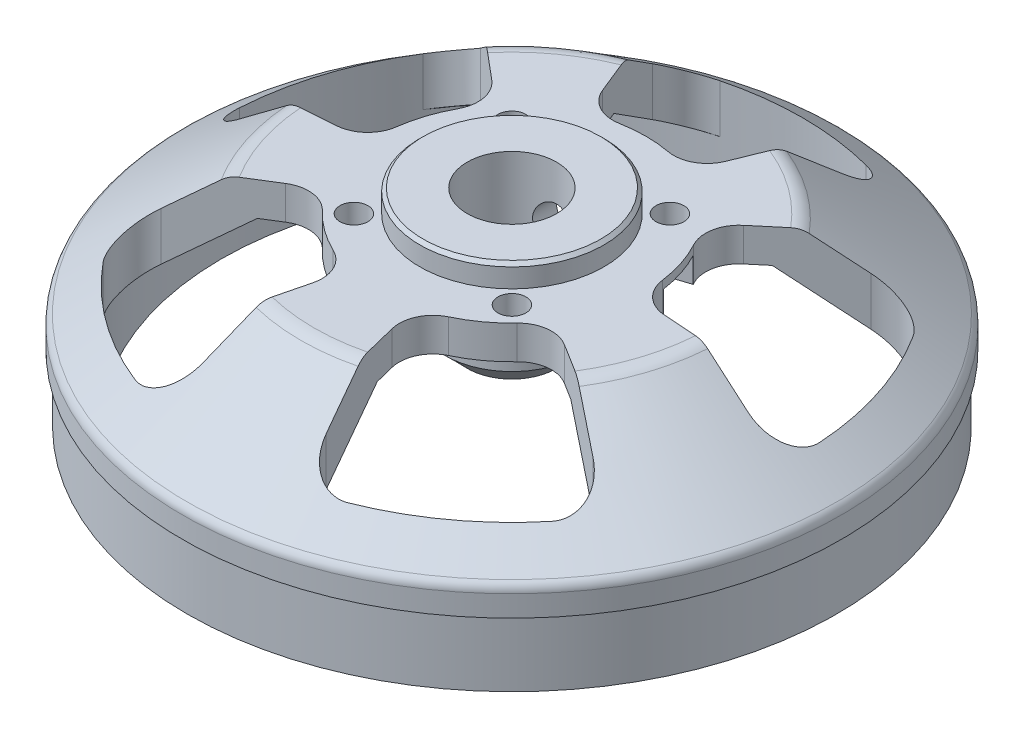
SolidWorks part; units mm, degrees
ref_plane "Front Plane" through (0, 0, 0) normal (0, 0, 1) x (1, 0, 0)
ref_plane "Top Plane" through (0, 0, 0) normal (0, 1, 0) x (1, 0, 0)
ref_plane "Right Plane" through (0, 0, 0) normal (1, 0, 0) x (0, 0, -1)
sketch "Sketch1" plane through (0, 0, 0) normal (0, 1, 0) x (1, 0, 0)
  circle A1 centre (0, 0) radius 29.075
  circle A2 centre (0, 0) radius 26
  dimension "D1" = 58.15
extrude "Boss-Extrude1" add sketch "Sketch1" against normal blind 6
sketch "Sketch2" plane through (0, 0, 0) normal (0, 1, 0) x (1, 0, 0)
  circle A0 centre (0, 0) radius 29.5
sketch "Sketch4" plane through (0, 0, 0) normal (1, 0, 0) x (0, 0, -1)
  line L0 (0, 0) -> (0, 21) construction
  line L1 (29.5, 0) -> (-29.5, 0) construction
  line L2 (29.5, 0) -> (26, 0)
  line L3 (-29.5, 0) -> (-29.5, 1.8909)
  line L4 (-29.0883, 2.6995) -> (-18.8915, 10.1173)
  line L5 (-17.715, 10.5) -> (-8.25, 10.5)
  line L6 (-4, 10.5) -> (-4, 7.5)
  line L7 (-4, 7.5) -> (-16.5398, 7.5)
  line L8 (-16.5398, 7.5) -> (-26, 0.618)
  line L9 (-26, 0.618) -> (-26, 0)
  line L10 (-7.95, 12.5) -> (-8.25, 12.2)
  line L11 (-4, 10.5) -> (-4, 12.5)
  line L12 (-26, 0) -> (-29.5, 0)
  line L13 (-4, 12.5) -> (-7.95, 12.5)
  line L14 (-8.25, 12.2) -> (-8.25, 10.5)
  arc A0 (-18.8915, 10.1173) -> (-17.715, 10.5) centre (-17.715, 8.5) cw
  arc A1 (-29.5, 1.8909) -> (-29.0883, 2.6995) centre (-28.5, 1.8909) cw
  point P15 (-8.25, 12.5)
  point P22 (-29.5, 2.4)
  dimension "D8" = 2
  dimension "D9" = 1
  dimension "D1" = 3
  dimension "D2" = 3.5
  dimension "D3" = 10.5
  dimension "D4" = 2.4
  dimension "D5" = 4
  dimension "D6" = 8.25
  dimension "D7" = 2
revolve "Revolve3" add sketch "Sketch4" angle 360 about L0 region at (0, 0.9454, 29.216)
sketch "Sketch5" plane through (0, 10.5, 0) normal (0, 1, 0) x (1, 0, 0)
  line L0 (0, 0) -> (0, 30.8593) construction
  line L1 (-5.5114, 13.6244) -> (-8.5513, 21.1394)
  line L2 (5.5114, 13.6244) -> (8.5513, 21.1394)
  arc A0 (2.1842, 11.7995) -> (-2.1842, 11.7995) centre (0, 0) ccw
  arc A1 (6.5229, 25.1685) -> (-6.5229, 25.1685) centre (0, 0) ccw
  circle A2 centre (0, 0) radius 29.5 construction
  arc A3 (-5.5114, 13.6244) -> (-2.1842, 11.7995) centre (-2.7303, 14.7494) ccw
  arc A4 (-6.5229, 25.1685) -> (-8.5513, 21.1394) centre (-5.7702, 22.2644) ccw
  arc A5 (6.5229, 25.1685) -> (8.5513, 21.1394) centre (5.7702, 22.2644) cw
  arc A6 (5.5114, 13.6244) -> (2.1842, 11.7995) centre (2.7303, 14.7494) cw
  point P13 (-9.75, 24.1026)
  dimension "D1" = 3.5
  dimension "D2" = 24
  dimension "D3" = 9.75
  dimension "D4" = 3
  dimension "D5" = 3
extrude "Cut-Extrude1" cut sketch "Sketch5" against normal through all
sketch "Sketch6" plane through (0, 0, 0) normal (0, 0, 1) x (1, 0, 0)
  line L0 (0, 0) -> (0, 15.3619) construction
pattern_circular "CirPattern1" count 5 over 360 about axis through (0, 0, 0) along (0, 1, 0) of "Cut-Extrude1" reverse direction yes
sketch "Sketch7" plane through (0, 10.5, 0) normal (0, 1, 0) x (1, 0, 0)
  circle A0 centre (0, 0) radius 10
  circle A1 centre (0, 10) radius 1.25
  arc A2 (-10.5471, 5.7236) -> (-11.897, 1.5689) centre (0, 0) ccw construction
  circle A3 centre (7.0711, 7.0711) radius 1.25
  circle A4 centre (10, 0) radius 1.25
  circle A5 centre (7.0711, -7.0711) radius 1.25
  circle A6 centre (0, -10) radius 1.25
  circle A7 centre (-7.0711, -7.0711) radius 1.25
  circle A8 centre (-10, 0) radius 1.25
  circle A9 centre (-7.0711, 7.0711) radius 1.25
  point P5 (-11.4127, 3.7082)
  point P26 (0, 0)
  dimension "D1" = 8
extrude "Cut-Extrude2" cut sketch "Sketch7" against normal through all contours A9 | A7 | A5 | A3
sketch "Sketch8" plane through (0, 7.5, 0) normal (0, -1, 0) x (-1, 0, 0)
  circle A0 centre (0, 0) radius 6
extrude "Boss-Extrude3" add sketch "Sketch8" along normal blind 7
chamfer "Chamfer2" distance 2 angle 45 1 edges at (0, 0.5, -6)
sketch "Sketch9" plane through (0, 0.5, 0) normal (0, -1, 0) x (-1, 0, 0)
  circle A0 centre (0, 0) radius 4
  dimension "D1" = 8
extrude "Cut-Extrude3" cut sketch "Sketch9" against normal through all
ref_plane "Plane2" through (0, 0, -11.7995) normal (0, 0, -1) x (-1, 0, 0)
sketch "Sketch10" plane through (0, 7.5, 0) normal (0, -1, 0) x (1, 0, 0)
  line L0 (2.075, -15.925) -> (2.075, -8.075)
  line L1 (2.075, -15.925) -> (-2.075, -15.925)
  line L2 (2.075, -8.075) -> (-2.075, -8.075)
  line L3 (-2.075, -15.925) -> (-2.075, -8.075)
  line L4 (2.075, -15.925) -> (-2.075, -8.075) construction
  line L5 (2.075, -8.075) -> (-2.075, -15.925) construction
  arc A0 (-2.1842, -11.7995) -> (2.1842, -11.7995) centre (0, 0) ccw construction
  arc A1 (2.075, -8.075) -> (-2.075, -8.075) centre (0, -8.075) ccw
  circle A2 centre (0, 0) radius 6 construction
  point P0 (0, -12)
  point P1 (0, -12)
  point P10 (0, -6)
  point P11 (0, -6)
  arc M15 (-2.1842, -11.7995) -> (2.1842, -11.7995) centre (0, 0) ccw
  dimension "D1" = 4.15
  dimension "D2" = 0
  dimension "D3" = 0
extrude "Cut-Extrude4" cut sketch "Sketch10" against normal blind 2.25 contours L3 L0 L2 M15 | L2 A1 region at (0, 7.5, -10.0078) region at (0, 7.5, -7.1943)
sketch "Sketch11" plane through (0, 0, -11.7995) normal (0, 0, -1) x (-1, 0, 0)
  line L0 (0, 7.5) -> (2.075, 7.5) construction
  line L1 (0, 7.5) -> (2.075, 7.5)
  circle A0 centre (0, 7.5) radius 1.75
  dimension "D1" = 3.5
extrude "Cut-Extrude5" cut sketch "Sketch11" against normal blind 11 contours A0
pattern_circular "CirPattern2" count 2 over 72 about axis through (0, 0, 0) along (0, 1, 0) of "Cut-Extrude4", "Cut-Extrude5" reverse direction yes
